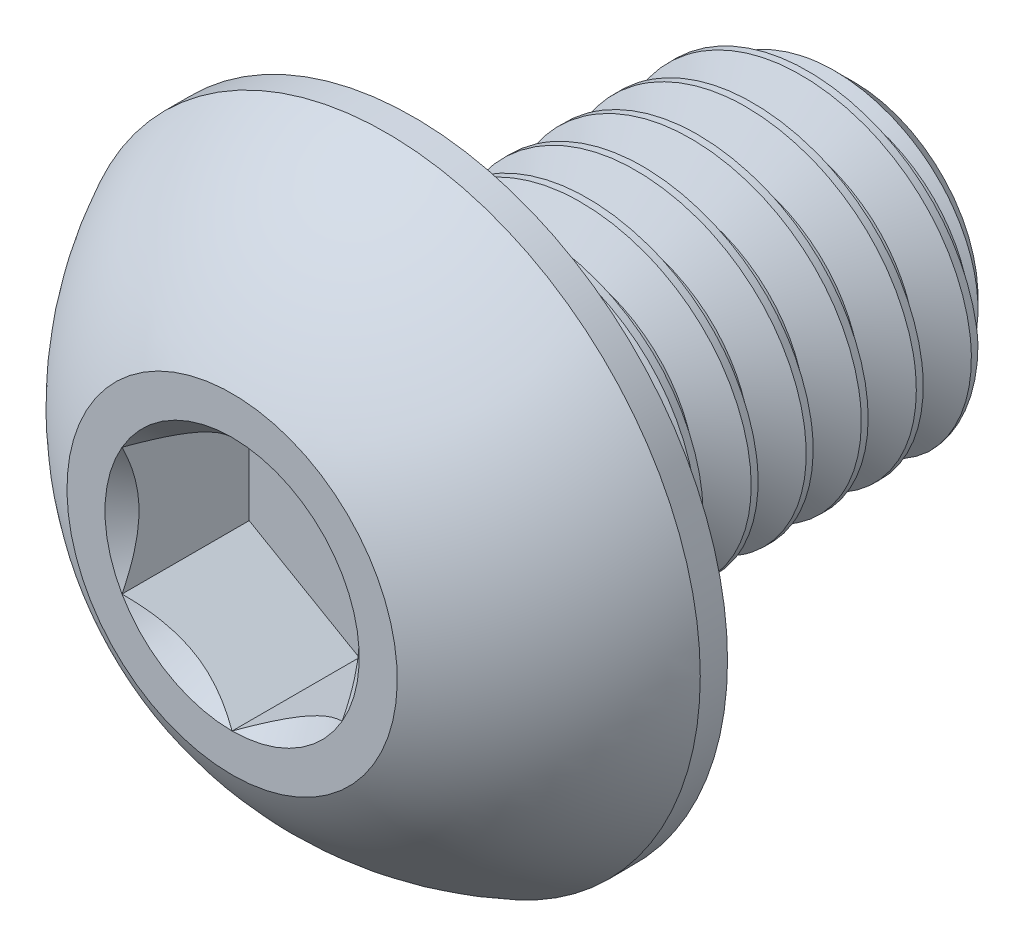
SolidWorks part; units mm, degrees
ref_plane "Front" through (0, 0, 0) normal (0, 0, 1) x (1, 0, 0)
ref_plane "Top" through (0, 0, 0) normal (0, 1, 0) x (1, 0, 0)
ref_plane "Right" through (0, 0, 0) normal (1, 0, 0) x (0, 0, -1)
sketch "Sketch1" plane through (0, 0, 0) normal (1, 0, 0) x (0, 0, -1)
  line L2 (1.65, 1.5) -> (5.65, 1.5)
  line L3 (5.65, 1.5) -> (5.65, 0)
  line L4 (5.65, 0) -> (1.65, 0)
  line L6 (1.4025, 2.85) -> (1.65, 2.85) construction
  line L7 (5.65, 1.5) -> (5.65, -1.5) construction
  line L8 (0, 0) -> (1.65, 0) construction
  line L9 (1.65, 2.85) -> (1.65, -2.85) construction
  line L11 (1.65, 1.5) -> (1.65, 0)
  line L13 (0, 1) -> (0, -1) construction
  line L14 (0, 1) -> (0, 1.5) construction
  arc A3 (0, 1.5) -> (1.4025, 2.85) centre (2.7948, 0) cw construction
  dimension "D1" = 0.2475
  dimension "Head Ht" = 1.65
  dimension "Head Dia" = 5.7
  dimension "Dia" = 3
  dimension "Lg" = 4
  dimension "Hex" = 2
revolve "Revolve1" add sketch "Sketch1" angle 360 about L4
sketch "Sketch3" plane through (0, 0, -5.65) normal (0, 0, -1) x (-1, 0, 0)
  circle A0 centre (0, 0) radius 1.5
curve "Helix/Spiral1" pitch 0.5 height 4.5 radius 1.5 centre (0, 0, -5.65) axis (0, 0, 1) start towards (0, 1, 0)
sketch "Sketch2" plane through (0, 0, 0) normal (1, 0, 0) x (0, 0, -1)
  line L0 (5.65, 1.5) -> (6.0875, 1.5)
  line L1 (6.0875, 1.5) -> (5.9, 1.1752)
  line L2 (5.9, 1.1752) -> (5.8375, 1.1752)
  line L3 (5.8375, 1.1752) -> (5.65, 1.5)
  line L4 (5.7438, 1.3376) -> (5.9938, 1.3376) construction
  dimension "D1" = 60
  dimension "D2" = 0.0625
  dimension "D3" = 0.25
chamfer "Chamfer1" distance 0.375 angle 45 1 edges at (0, 1.5, -5.65)
sweep "Cut-Sweep1" cut profiles "Sketch2" path "Helix/Spiral1"
sketch "Sketch7" plane through (0, 0, 0) normal (1, 0, 0) x (0, 0, -1)
  line L6 (1.4025, 2.85) -> (1.65, 2.85) construction
  line L8 (0, 0) -> (1.65, 0) construction
  line L11 (1.65, 2.85) -> (1.65, -2.85) construction
  line L12 (1.4025, 2.85) -> (1.65, 2.85)
  line L13 (0, 0) -> (1.65, 0)
  line L14 (0, 1) -> (0, -1) construction
  line L15 (1.65, 2.85) -> (1.65, 0)
  line L16 (0, 1.5) -> (0, 0)
  arc A2 (1.4025, 2.85) -> (0, 1.5) centre (2.7948, 0) ccw construction
  arc A3 (1.4025, 2.85) -> (0, 1.5) centre (2.7948, 0) ccw
revolve "Revolve2" add sketch "Sketch7" angle 360 about L13
sketch "Sketch5" plane through (0, 0, 0) normal (0, 0, 1) x (1, 0, 0)
  line L1 (1, -0.5774) -> (1, 0.5774)
  line L2 (1, 0.5774) -> (0, 1.1547)
  line L3 (0, 1.1547) -> (-1, 0.5774)
  line L4 (-1, 0.5774) -> (-1, -0.5774)
  line L5 (-1, -0.5774) -> (0, -1.1547)
  line L6 (0, -1.1547) -> (1, -0.5774)
  circle A0 centre (0, 0) radius 1 construction
extrude "Cut-Extrude2" cut sketch "Sketch5" against normal blind 1.155
sketch "Sketch6" plane through (0, 0, 0) normal (0, 0, 1) x (1, 0, 0)
  circle A0 centre (0, 0) radius 1.1547
extrude "Cut-Extrude3" cut sketch "Sketch6" against normal blind 1.155 draft 45
sketch "Sketch9" [suppressed] plane through (0, 0, -4.2164) normal (0, 0, 1) x (1, 0, 0)
  circle A2 centre (0, 0) radius 3.9687
extrude "Boss-Extrude2" [suppressed] add sketch "Sketch9" against normal offset from surface (9.525 mm away) 28.575 up to face at (0, 1.125, -5.65)
sketch "Sketch10" plane through (0, 0, 0) normal (1, 0, 0) x (0, 0, -1)
  line L0 (5.65, 1.5) -> (5.65, -1.5) construction
  point P0 (4.9, -1.5)
  dimension "D1" = 0.75
equation "\"D3@Helix/Spiral1\" = \"Lg@Sketch1\" + \"D4@Helix/Spiral1\""
equation "\"D2@Sketch2\" = \"D4@Helix/Spiral1\" * .125"
equation "\"D3@Sketch2\" = \"D4@Helix/Spiral1\" * .5"
equation "\"D1@Chamfer1\" = \"D4@Helix/Spiral1\" * .75"
equation "\"D1@Cut-Extrude2\" = \"Head Ht@Sketch1\" * .7"
equation "\"D1@Sketch1\" = \"Head Ht@Sketch1\" * .15"
equation "\"D1@Sketch10\" = \"D4@Helix/Spiral1\" * 1.5"
equation "\"D1@Cut-Extrude3\" = \"D1@Cut-Extrude2\""
